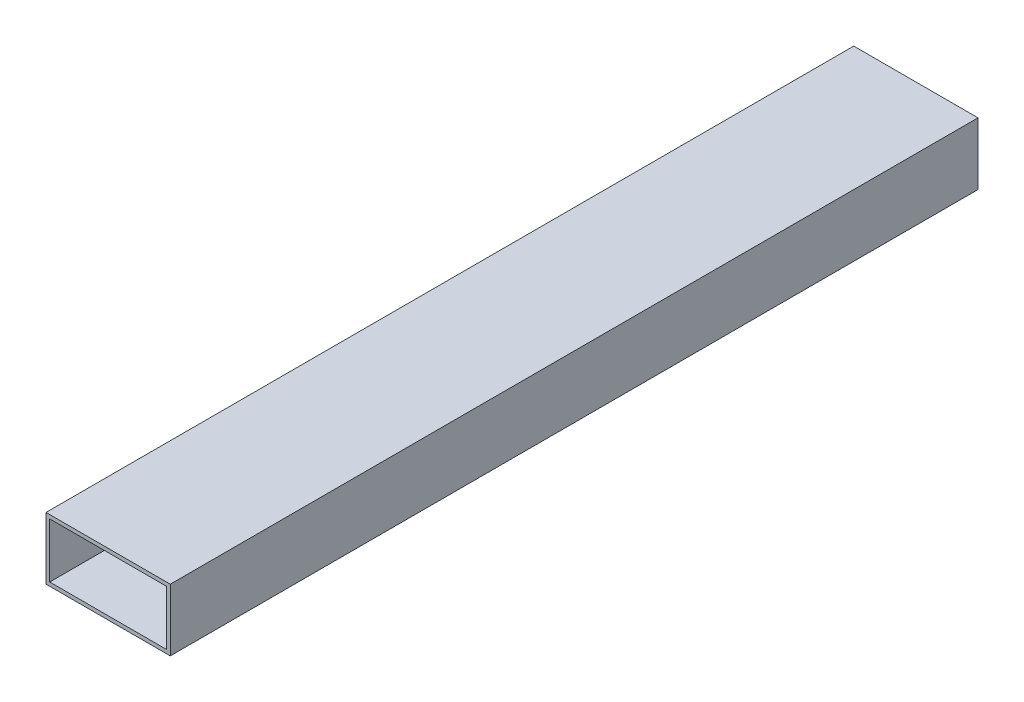
SolidWorks part; units mm, degrees
ref_plane "Front Plane" through (0, 0, 0) normal (0, 0, 1) x (1, 0, 0)
ref_plane "Top Plane" through (0, 0, 0) normal (0, 1, 0) x (1, 0, 0)
ref_plane "Right Plane" through (0, 0, 0) normal (1, 0, 0) x (0, 0, -1)
sketch "Sketch1" plane through (0, 0, 0) normal (0, 0, 1) x (1, 0, 0)
  line L1 (0, 0) -> (-50.8, 0)
  line L2 (0, 0) -> (0, 25.4)
  line L3 (0, 25.4) -> (-50.8, 25.4)
  line L4 (-50.8, 0) -> (-50.8, 25.4)
  dimension "D1" = 50.8
  dimension "D2" = 25.4
extrude "Extrude-Thin1" add sketch "Sketch1" along normal blind 330.2 thin thin type one direction reverse wall 1.524
